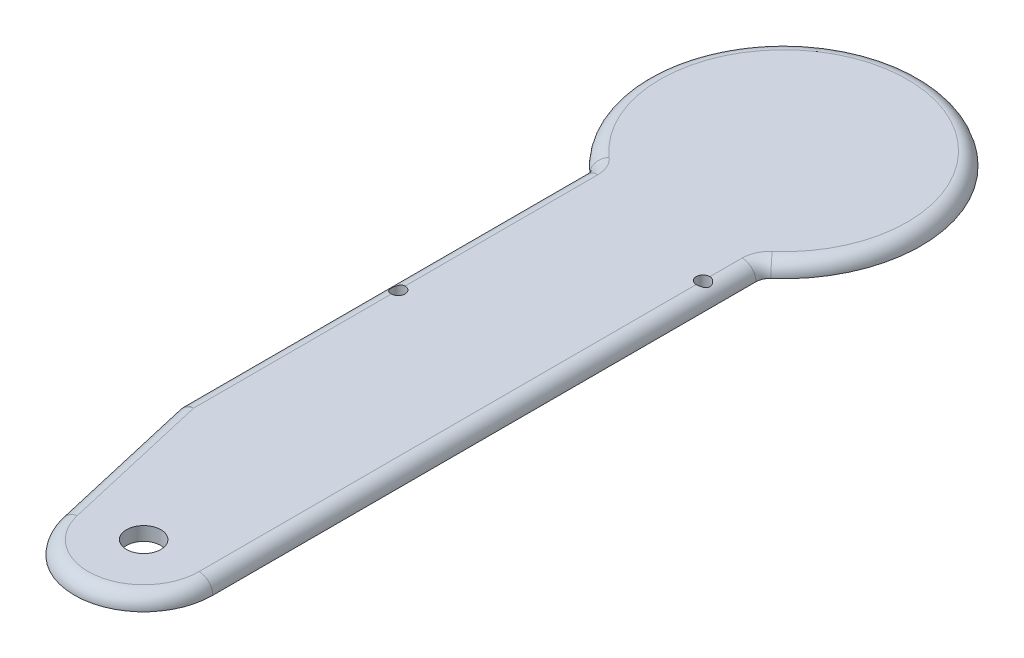
SolidWorks part; units mm, degrees
ref_plane "Front Plane" through (0, 0, 0) normal (0, 0, 1) x (1, 0, 0)
ref_plane "Top Plane" through (0, 0, 0) normal (0, 1, 0) x (1, 0, 0)
ref_plane "Right Plane" through (0, 0, 0) normal (1, 0, 0) x (0, 0, -1)
sketch "Sketch1" plane through (0, 0, 0) normal (0, 1, 0) x (1, 0, 0)
  line L0 (-15.875, -19.8279) -> (-15.875, -96.0279)
  line L1 (-15.875, -96.0279) -> (-9.3624, -124.2973)
  line L3 (15.875, -96.0279) -> (15.875, -19.8279)
  line L6 (-15.875, -19.8279) -> (15.875, -19.8279) construction
  line L7 (0, -19.8279) -> (0, 0) construction
  line L8 (-13.335, -57.9279) -> (-15.875, -57.9279) construction
  line L9 (13.335, -28.2506) -> (15.875, -28.2506) construction
  line L11 (15.875, -96.0279) -> (15.875, -121.4279)
  arc A0 (15.875, -19.8279) -> (-15.875, -19.8279) centre (0, 0) ccw
  arc A8 (-9.3624, -124.2973) -> (15.875, -121.4279) centre (3.0932, -121.4279) ccw
  circle A9 centre (3.0932, -121.4279) radius 3.175
  circle A10 centre (-13.335, -57.9279) radius 1.27
  circle A11 centre (13.335, -28.2506) radius 1.27
  dimension "D3" = 50.8
  dimension "D9" = 6.35
  dimension "D10" = 2.54
  dimension "D5" = 76.2
  dimension "D6" = 101.6
  dimension "D7" = 31.75
  dimension "D8" = 25.4
  dimension "D11" = 2.54
extrude "Boss-Extrude1" add sketch "Sketch1" along normal blind 2.54
fillet "Fillet1" radius 2.54 3 edges at (-15.875, 1.27, 96.0279) (-15.875, 1.27, 19.8279) (15.875, 1.27, 19.8279)
fillet "Fillet2" radius 2.54 8 edges at (-16.1016, 2.54, 19.964) (0, 2.54, -25.4) (16.1016, 2.54, 19.964) (15.875, 2.54, 71.2203) (4.5372, 2.54, 134.1279) (-12.5863, 2.54, 110.3033) (-15.8587, 2.54, 96.026) (-15.875, 2.54, 58.3759)
